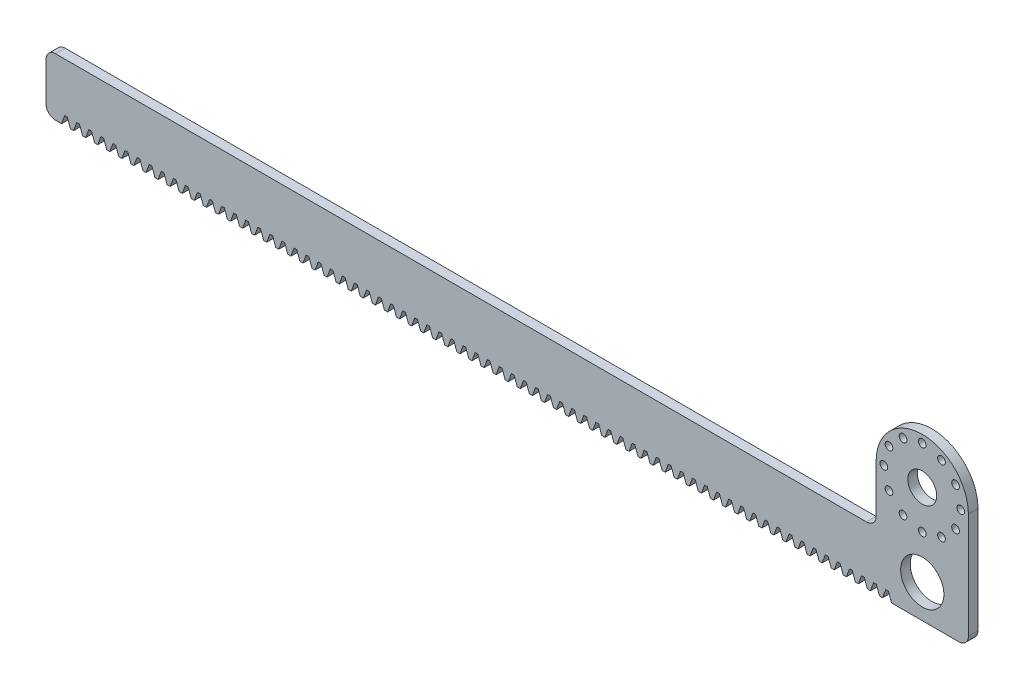
SolidWorks part; units mm, degrees
material "PC High Viscosity"
ref_plane "Front Plane" through (0, 0, 0) normal (0, 0, 1) x (1, 0, 0)
ref_plane "Top Plane" through (0, 0, 0) normal (0, 1, 0) x (1, 0, 0)
ref_plane "Right Plane" through (0, 0, 0) normal (1, 0, 0) x (0, 0, -1)
sketch "Sketch1" plane through (0, 0, 0) normal (0, 0, 1) x (1, 0, 0)
  line L2 (0, 0) -> (0, 38.1)
  line L3 (0, 38.1) -> (40.5308, 38.1)
  line L8 (40.5308, 38.1) -> (548.64, 38.1)
  line L9 (0, 0) -> (609.6, 0)
  line L19 (590.55, 0) -> (590.55, 10.0162) construction
  line L20 (590.55, 10.0162) -> (76.2, 10.0162) construction
  line L21 (76.2, 10.0162) -> (76.2, 0) construction
  line L22 (609.6, 76.2) -> (609.6, 0)
  line L27 (548.64, 76.2) -> (548.64, 38.1)
  line L28 (560.3214, 25.4803) -> (569.7207, 77.8858) construction
  line L29 (588.5193, 77.8858) -> (597.9186, 25.4803) construction
  circle A1 centre (579.12, 76.2) radius 9.525
  circle A2 centre (579.12, 76.2) radius 25.4 construction
  circle A3 centre (579.12, 101.6) radius 2.54
  circle A4 centre (591.82, 98.197) radius 2.54
  circle A5 centre (601.117, 88.9) radius 2.54
  circle A6 centre (604.52, 76.2) radius 2.54
  circle A7 centre (601.117, 63.5) radius 2.54
  circle A8 centre (591.82, 54.203) radius 2.54
  circle A9 centre (579.12, 50.8) radius 2.54
  circle A10 centre (566.42, 54.203) radius 2.54
  circle A11 centre (557.123, 63.5) radius 2.54
  circle A12 centre (553.72, 76.2) radius 2.54
  circle A13 centre (557.123, 88.9) radius 2.54
  circle A14 centre (566.42, 98.197) radius 2.54
  arc A15 (609.6, 76.2) -> (548.64, 76.2) centre (579.12, 76.2) ccw
  circle A16 centre (557.123, 88.9) radius 5.08 construction
  arc A17 (588.5193, 77.8858) -> (569.7207, 77.8858) centre (579.12, 76.2) ccw construction
  arc A18 (560.3214, 25.4803) -> (597.9186, 25.4803) centre (579.12, 22.1086) ccw construction
  circle A19 centre (579.12, 22.1086) radius 14.2875
  point P48 (579.12, 76.2)
  dimension "D3" = 5.08
  dimension "D4" = 50.8
  dimension "D9" = 10.16
  dimension "D5" = 19.05
  dimension "D12" = 28.575
  dimension "D2" = 38.1
  dimension "D1" = 609.6
  dimension "D7" = 76.2
  dimension "D8" = 38.1
  dimension "D6" = 12
extrude "Boss-Extrude1" add sketch "Sketch1" along normal blind 6.35 contours L3 | L3 L2 region at (332.535, 25.1889, 0)
fillet "Fillet2" radius 6.35 4 edges at (0, 38.1, 3.175) (0, 0, 3.175) (548.64, 38.1, 3.175) (609.6, 0, 3.175)
sketch "Sketch2" plane through (0, 0, 6.35) normal (0, 0, 1) x (1, 0, 0)
  line L0 (558.8, 0) -> (43.7057, 0)
  line L1 (43.7057, 0) -> (43.7057, 5.715)
  line L2 (43.7057, 5.715) -> (558.8, 5.715)
  line L3 (558.8, 5.715) -> (558.8, 0)
  line L5 (557.8755, 2.54) -> (549.711, 2.54) construction
  line L6 (558.8, 0) -> (556.7199, 5.715)
  line L7 (609.6, 76.2) -> (609.6, 6.35) construction
  line L8 (552.8688, 0) -> (558.8, 0)
  line L10 (556.7199, 5.715) -> (554.9488, 5.715)
  line L11 (558.8, 0) -> (552.8688, 0)
  line L12 (552.8688, 0) -> (554.9488, 5.715)
  line L13 (554.9488, 5.715) -> (556.7199, 5.715)
  line L14 (558.8, 0) -> (552.8688, 0)
  line L15 (554.9488, 5.715) -> (556.7199, 5.715)
  line L16 (558.8, 0) -> (552.8688, 0)
  line L17 (552.8688, 0) -> (558.8, 0)
  line L19 (556.7199, 5.715) -> (554.9488, 5.715) construction
  line L20 (552.8688, 0) -> (558.8, 0) construction
  line L23 (0, 0) -> (609.6, 0) construction
  point P8 (553.7932, 2.54)
  point P16 (557.8755, 2.54)
  dimension "D1" = 70
  dimension "D2" = 2.54
  dimension "D3" = 3.175
  dimension "D4" = 70
  dimension "D5" = 1.7711
  dimension "D6" = 50.8
  dimension "D7" = 515.0943
extrude "Cut-Extrude1" cut sketch "Sketch2" against normal through all contours L12 L0 L8 L6 L2 region at (555.8344, 2.343, 6.35)
pattern_linear "LPattern1" count 69 spacing 7.9796 along (-1, 0, 0) of "Cut-Extrude1"
equation "\"D11@Sketch1\"=(24*5mm)/pi"
equation "\"D10@Sketch1\"=(12*5mm)/pi"
equation "\"D13@Sketch1\"=(40*5mm)-0.005"
